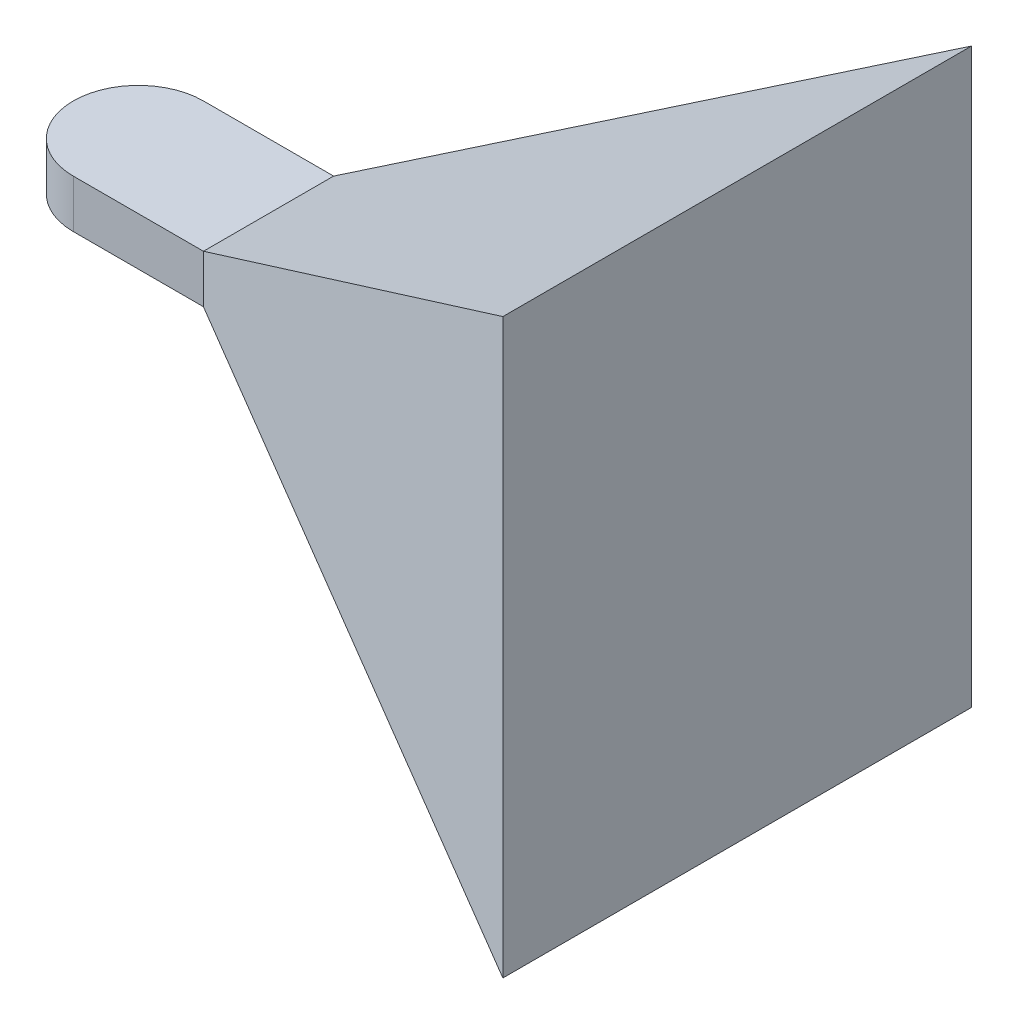
SolidWorks part; units mm, degrees
material "Custom Plastic"
ref_plane "Front Plane" through (0, 0, 0) normal (0, 0, 1) x (1, 0, 0)
ref_plane "Top Plane" through (0, 0, 0) normal (0, 1, 0) x (1, 0, 0)
ref_plane "Right Plane" through (0, 0, 0) normal (1, 0, 0) x (0, 0, -1)
sketch "Sketch1" plane through (0, 0, 0) normal (0, 1, 0) x (1, 0, 0)
  line L0 (0, 31.75) -> (63.5, 31.75)
  line L1 (0, -31.75) -> (63.5, -31.75)
  line L2 (63.5, 31.75) -> (292.1, 114.3)
  line L3 (292.1, 114.3) -> (292.1, -114.3)
  line L4 (292.1, -114.3) -> (63.5, -31.75)
  line L5 (0, 0) -> (292.1, 0) construction
  arc A0 (0, 31.75) -> (0, -31.75) centre (0, 0) ccw
  dimension "D1" = 63.5
  dimension "D2" = 63.5
  dimension "D3" = 228.6
  dimension "D4" = 228.6
extrude "Boss-Extrude1" add sketch "Sketch1" along normal blind 139.7 and the other way blind 139.7
sketch "Sketch2" plane through (0, 0, 0) normal (0, 0, 1) x (1, 0, 0)
  line L0 (-31.75, 11.7239) -> (63.5, 11.7239)
  line L1 (-31.75, 139.7) -> (-31.75, -139.7) construction
  line L2 (63.5, -139.7) -> (63.5, 139.7) construction
  line L3 (63.5, 11.7239) -> (292.1, 139.7)
  line L4 (0, 0) -> (44.7325, 0) construction
  line L5 (63.5, -11.7239) -> (292.1, -139.7)
  line L6 (-31.75, -11.7239) -> (63.5, -11.7239)
  line L7 (-31.75, 11.7239) -> (-31.75, 139.7)
  line L8 (-31.75, 139.7) -> (292.1, 139.7)
  line L9 (-31.75, -11.7239) -> (-31.75, -139.7)
  line L10 (-31.75, -139.7) -> (292.1, -139.7)
extrude "Cut-Extrude1" cut sketch "Sketch2" against normal blind 139.7 and the other way blind 139.7
